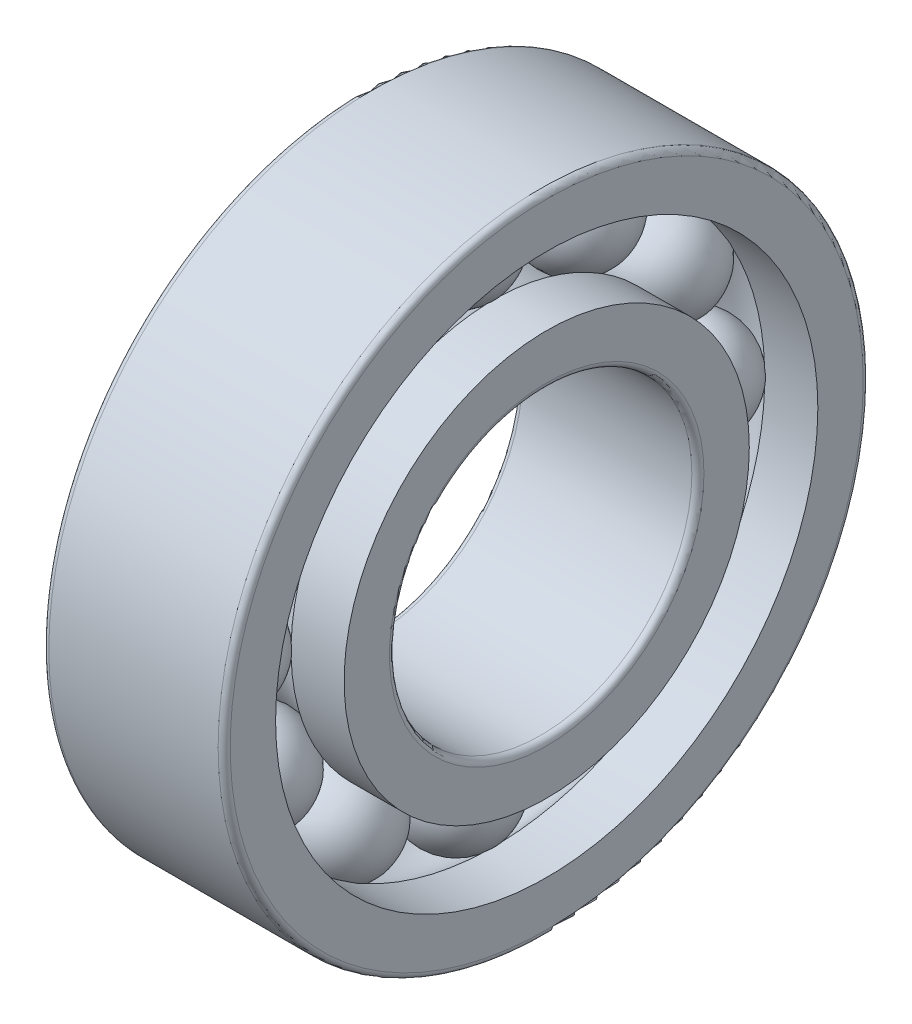
SolidWorks part; units mm, degrees
ref_plane "Plane1" through (0, 0, 0) normal (0, 0, 1) x (1, 0, 0)
ref_plane "Plane2" through (0, 0, 0) normal (0, 1, 0) x (1, 0, 0)
ref_plane "Plane3" through (0, 0, 0) normal (1, 0, 0) x (0, 0, -1)
sketch "Clipboard" plane through (0, 0, 0) normal (0, 0, 1) x (1, 0, 0)
  line L0 (-10, 0) -> (10, 0) construction
  line L1 (0, 0) -> (21.872, -4.649)
  line L2 (0, 0) -> (11.4932, 2.443)
  line L3 (0, 0) -> (21.872, -4.649)
  line L4 (0, 0) -> (-22.3573, -0.3902)
  dimension "BallCLRad" = 11.75
  dimension "Count" = 12
  dimension "Show_count" = 12
  dimension "Max_count" = 12
  dimension "Min_count" = 1
sketch "CagSpiSke" plane through (0, 0, 0) normal (0, 0, 1) x (1, 0, 0)
  line L0 (0.255, 11.325) -> (0.255, 12.175)
  line L1 (0.255, 12.175) -> (-0.255, 12.175)
  line L2 (-0.255, 12.175) -> (-0.255, 11.325)
  line L3 (-0.255, 11.325) -> (0.255, 11.325)
  line L4 (-20.6375, 0) -> (20.6375, 0) construction
  line L5 (0, 0) -> (0, 23.7692) construction
  dimension "Thickness" = 0.51
  dimension "OD" = 24.35
  dimension "ID" = 22.65
revolve "CageSpine" add sketch "CagSpiSke" angle 0.001 about L4 reverse direction yes
ref_axis "Axis1" through (-50, 0, 0) along (1, 0, 0)
sketch "CagBalSke" plane through (0, 0, 0) normal (0, 0, 1) x (1, 0, 0)
  line L0 (-2.805, 11.75) -> (2.805, 11.75)
  line L1 (-1.905, 11.75) -> (1.905, 11.75) construction
  line L2 (-10, 0) -> (10, 0) construction
  line L3 (0, 0) -> (0, 24) construction
  arc A0 (2.805, 11.75) -> (-2.805, 11.75) centre (0, 11.75) cw
  dimension "CageWallOD" = 5.61
  dimension "BallCLRad" = 11.75
revolve "CageBall" [suppressed] add sketch "CagBalSke" angle 360 about L1 reverse direction yes
pattern_circular "CageBalls" [suppressed] count 12 every 30 about axis through (-50, 0, 0) along (1, 0, 0)
sketch "CagTrmODSke" plane through (0, 0, 0) normal (0, 0, 1) x (1, 0, 0)
  line L0 (2.806, 12.175) -> (2.806, 14.556)
  line L1 (2.806, 14.556) -> (-2.806, 14.556)
  line L2 (-2.806, 14.556) -> (-2.806, 12.175)
  line L3 (-2.806, 12.175) -> (2.806, 12.175)
  line L4 (-20.6375, 0) -> (20.6375, 0) construction
  line L5 (0, 0) -> (0, 25) construction
  dimension "Width" = 5.612
  dimension "ID" = 24.35
  dimension "OD" = 29.112
revolve "CageTrimOD" [suppressed] cut sketch "CagTrmODSke" angle 360 about L4 reverse direction yes
sketch "CagTrmIDSke" plane through (0, 0, 0) normal (0, 0, 1) x (1, 0, 0)
  line L0 (2.806, 8.946) -> (2.806, 11.325)
  line L1 (2.806, 11.325) -> (-2.806, 11.325)
  line L2 (-2.806, 11.325) -> (-2.806, 8.946)
  line L3 (-2.806, 8.946) -> (2.806, 8.946)
  line L4 (-20.6375, 0) -> (20.6375, 0) construction
  line L5 (0, 0) -> (0, 25) construction
  dimension "ID" = 17.892
  dimension "OD" = 22.65
  dimension "Width" = 5.612
revolve "CageTrimID" [suppressed] cut sketch "CagTrmIDSke" angle 360 about L4 reverse direction yes
sketch "BalSimSke" plane through (0, 0, 0) normal (0, 0, 1) x (1, 0, 0)
  line L0 (-10, 0) -> (10, 0) construction
  line L1 (-10, 11.75) -> (10, 11.75) construction
  line L2 (0, 0) -> (0, 23) construction
  circle A0 centre (0, 11.75) radius 2.55
  dimension "Ball_diameter" = 5.1
  dimension "BallCLRad" = 11.75
revolve "BallsSimplified" [suppressed] add sketch "BalSimSke" angle 360 about L0
sketch "BalDetSke" plane through (0, 0, 0) normal (0, 0, 1) x (1, 0, 0)
  line L0 (-2.55, 11.75) -> (2.55, 11.75)
  line L1 (-1.905, 11.75) -> (1.905, 11.75) construction
  line L2 (0, 0) -> (0, 25) construction
  arc A0 (2.55, 11.75) -> (-2.55, 11.75) centre (0, 11.75) cw
  dimension "Ball_diameter" = 5.1
  dimension "BallCLRad" = 11.75
revolve "BallDetailed" add sketch "BalDetSke" angle 360 about L1 reverse direction yes
sketch "InnRacSke" plane through (0, 0, 0) normal (0, 0, 1) x (1, 0, 0)
  line L0 (-1.867, 10.05) -> (-4.5, 10.05)
  line L1 (-4.5, 10.05) -> (-4.5, 7.8)
  line L2 (-4.2, 7.5) -> (4.2, 7.5)
  line L3 (4.5, 7.8) -> (4.5, 10.05)
  line L4 (4.5, 10.05) -> (1.867, 10.05)
  line L5 (-20.6375, 0) -> (20.6375, 0) construction
  line L6 (0, 0) -> (0, 30) construction
  arc A0 (-4.5, 7.8) -> (-4.2, 7.5) centre (-4.2, 7.8) ccw
  arc A1 (4.2, 7.5) -> (4.5, 7.8) centre (4.2, 7.8) ccw
  arc A2 (1.867, 10.05) -> (-1.867, 10.05) centre (0, 11.75) cw
  dimension "Fillet_radius" = 0.3
  dimension "Ball_diameter" = 5.05
  dimension "ID" = 15
  dimension "OD" = 20.1
  dimension "Width" = 9
  dimension "BallCLRad" = 11.75
revolve "InnerRace" add sketch "InnRacSke" angle 360 about L5 reverse direction yes
sketch "OutRacSke" plane through (0, 0, 0) normal (0, 0, 1) x (1, 0, 0)
  line L0 (-1.867, 13.45) -> (-4.5, 13.45)
  line L1 (-4.5, 13.45) -> (-4.5, 15.7)
  line L2 (-4.2, 16) -> (4.2, 16)
  line L3 (4.5, 15.7) -> (4.5, 13.45)
  line L4 (4.5, 13.45) -> (1.867, 13.45)
  line L5 (-20.6375, 0) -> (20.6375, 0) construction
  line L6 (0, 0) -> (0, 30) construction
  arc A0 (-4.5, 15.7) -> (-4.2, 16) centre (-4.2, 15.7) cw
  arc A1 (4.2, 16) -> (4.5, 15.7) centre (4.2, 15.7) cw
  arc A2 (1.867, 13.45) -> (-1.867, 13.45) centre (0, 11.75) ccw
  dimension "Fillet_radius" = 0.3
  dimension "Ball_diameter" = 5.05
  dimension "OD" = 32
  dimension "ID" = 26.9
  dimension "Width" = 9
  dimension "BallCLRad" = 11.75
revolve "OuterRace" add sketch "OutRacSke" angle 360 about L5 reverse direction yes
pattern_circular "BallsDetailed" count 12 every 30 about axis through (-50, 0, 0) along (1, 0, 0) of "BallDetailed"
equation "\"BallCLRad@Clipboard\" = ( \"OD@OutRacSke\" + \"ID@InnRacSke\" ) / 4"
equation "\"BallCLRad@BalSimSke\" = \"BallCLRad@Clipboard\""
equation "\"BallCLRad@BalDetSke\" = \"BallCLRad@Clipboard\""
equation "\"BallCLRad@InnRacSke\" = \"BallCLRad@Clipboard\""
equation "\"BallCLRad@OutRacSke\" = \"BallCLRad@Clipboard\""
equation "\"Ball_diameter@InnRacSke\" = \"Ball_diameter@BalDetSke\" - 0.05"
equation "\"Ball_diameter@OutRacSke\" = \"Ball_diameter@BalDetSke\" - 0.05"
equation "\"Ball_diameter@BalSimSke\" = \"Ball_diameter@BalDetSke\""
equation "\"Width@OutRacSke\" = \"Width@InnRacSke\""
equation "\"Fillet_radius@OutRacSke\" = \"Fillet_radius@InnRacSke\""
equation "\"Max_count@Clipboard\" = int( 3.14159265 / atn(( \"Ball_diameter@BalDetSke\" / 2) / sqr( \"BallCLRad@Clipboard\"  *  \"BallCLRad@Clipboard\" - ( \"Ball_diameter@BalDetSke\" / 2) *  ( \"Ball_diameter@BalDetSke\" / 2))))"
equation "\"Max_count@Clipboard\" = ((sgn( \"Max_count@Clipboard\" - \"Count@Clipboard\" )-1)*( \"Max_count@Clipboard\" - \"Count@Clipboard\" ))/-2+ \"Count@Clipboard\""
equation "\"Count@BallsDetailed\" = int( \"Show_count@Clipboard\" ) "
equation "\"Count@BallsDetailed\" = ((sgn( \"Count@BallsDetailed\" - \"Max_count@Clipboard\" )-1)*( \"Count@BallsDetailed\" - \"Max_count@Clipboard\" ))/-2+ \"Max_count@Clipboard\""
equation "\"Count@BallsDetailed\" = ((sgn( \"Count@BallsDetailed\" - \"Min_count@Clipboard\" )+1)*( \"Count@BallsDetailed\" - \"Min_count@Clipboard\"))/2 +\"Min_count@Clipboard\""
equation "\"Angle@BallsDetailed\" = 360.0 / \"Max_count@Clipboard\""
equation "\"BallCLRad@CagBalSke\" = \"BallCLRad@Clipboard\""
equation "\"Count@CageBalls\" = \"Count@BallsDetailed\""
equation "\"Angle@CageBalls\" = \"Angle@BallsDetailed\""
equation "\"Angle@CageSpine\" =  \"Angle@CageBalls\" * ( \"Count@CageBalls\" -1 + int( \"Count@CageBalls\" / \"Max_count@Clipboard\" ) )  + 0.001 -  int( \"Count@CageBalls\" / \"Max_count@Clipboard\" ) * 0.001"
equation "\"Angle@CageSpine\" =  \"Angle@CageSpine\" * int( \"Min_count@Clipboard\" / 2) + int(1 / \"Min_count@Clipboard\")  * 0.001"
equation "\"CageWallOD@CagBalSke\" =  \"Ball_diameter@BalDetSke\" * 1.1"
equation "\"Thickness@CagSpiSke\" =  \"Ball_diameter@BalDetSke\" * 0.1"
equation "\"OD@CagTrmODSke\" = \"BallCLRad@Clipboard\" * 2 + \"CageWallOD@CagBalSke\" + 0.002"
equation "\"ID@CagTrmODSke\" = \"BallCLRad@Clipboard\" * 2 + \"Ball_diameter@BalDetSke\" / 6"
equation "\"OD@CagTrmIDSke\" = \"BallCLRad@Clipboard\" * 2 - \"Ball_diameter@BalDetSke\" / 6"
equation "\"ID@CagTrmIDSke\" = \"BallCLRad@Clipboard\" * 2 - \"CageWallOD@CagBalSke\" + 0.002"
equation "\"OD@CagSpiSke\" = \"ID@CagTrmODSke\""
equation "\"ID@CagSpiSke\" = \"OD@CagTrmIDSke\""
equation "\"Width@CagTrmODSke\" = \"CageWallOD@CagBalSke\" + 0.002"
equation "\"Width@CagTrmIDSke\" = \"CageWallOD@CagBalSke\" + 0.002"
